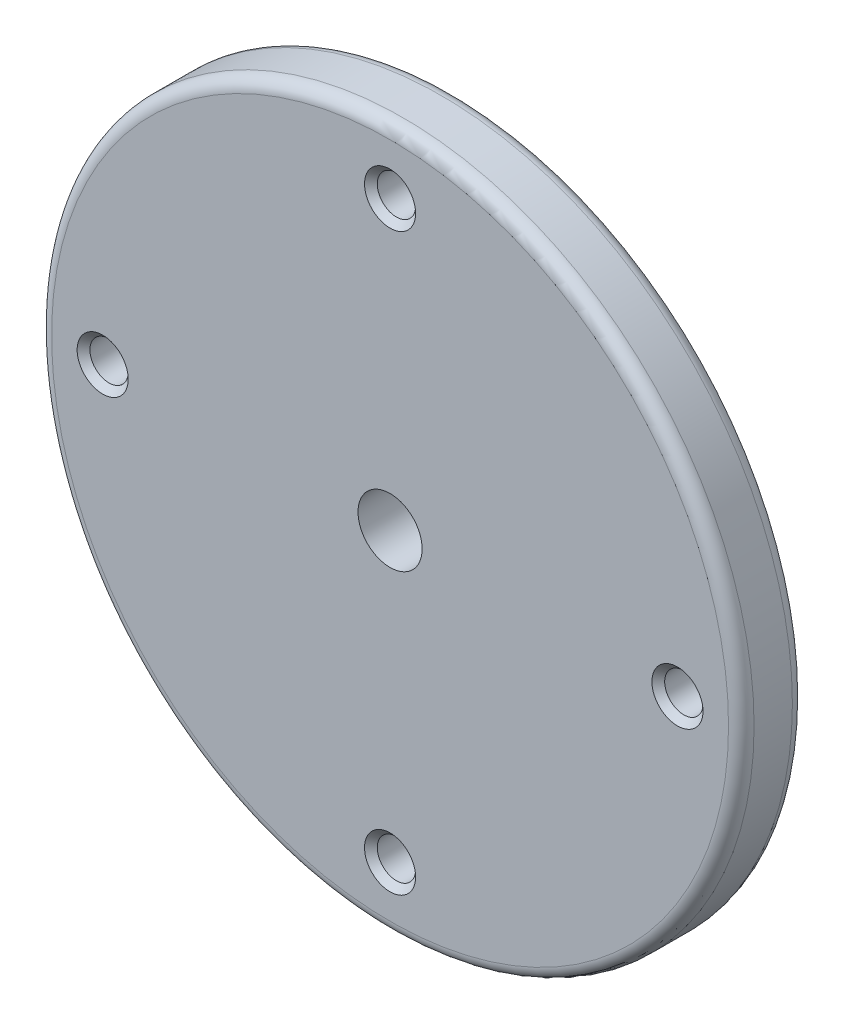
SolidWorks part; units mm, degrees
ref_plane "Plan de face" through (0, 0, 0) normal (0, 0, 1) x (1, 0, 0)
ref_plane "Plan de dessus" through (0, 0, 0) normal (0, 1, 0) x (1, 0, 0)
ref_plane "Plan de droite" through (0, 0, 0) normal (1, 0, 0) x (0, 0, -1)
sketch "Esquisse1" plane through (0, 0, 0) normal (0, 0, 1) x (1, 0, 0)
  line L0 (0, 48.0799) -> (0, -39.4045) construction
  circle A0 centre (0, 0) radius 27.5
  circle A1 centre (0, 0) radius 2.51
  circle A2 centre (0, 22.5) radius 1.5
  circle A3 centre (0, 0) radius 22.5
  circle A4 centre (22.5, 0) radius 1.5
  circle A5 centre (0, -22.5) radius 1.5
  circle A6 centre (-22.5, 0) radius 1.5
  point P18 (0, 0)
  dimension "D1" = 55
  dimension "D2" = 5.02
  dimension "D5" = 3
  dimension "D3" = 22.5
  dimension "D4" = 4
extrude "Boss.-Extru.2" add sketch "Esquisse1" along normal blind 5 contours L0 A0 A5 A3 A6 A2 | L0 A2 A3 A6 A5 A1 | A2 L0 A1 A5 A3 A4 | A0 L0 A2 A3 A4 A5 region at (19.0106, 19.0106, 0) region at (-0.6149, 25.75, 0) region at (-9.642, 0, 0) region at (9.642, 0, 0)
fillet "Congé1" radius 1 2 edges at (27.5, 0, 5) (27.5, 0, 0)
chamfer "Chanfrein1" distance 0.5 angle 45 4 edges at (24, 0, 5) (1.5, -22.5, 5) (-21, 0, 5) (1.5, 22.5, 5)
